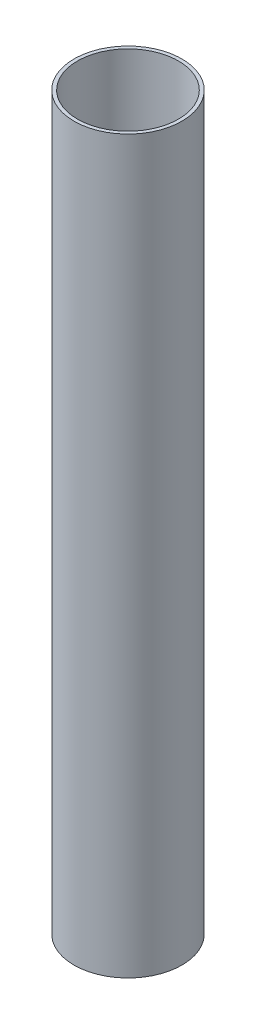
SolidWorks part; units mm, degrees
ref_plane "Front Plane" through (0, 0, 0) normal (0, 0, 1) x (1, 0, 0)
ref_plane "Top Plane" through (0, 0, 0) normal (0, 1, 0) x (1, 0, 0)
ref_plane "Right Plane" through (0, 0, 0) normal (1, 0, 0) x (0, 0, -1)
sketch "Sketch1" plane through (0, 0, 0) normal (0, 1, 0) x (1, 0, 0)
  circle A0 centre (0, 0) radius 14.5
  circle A1 centre (0, 0) radius 15.5
  dimension "D1" = 29
  dimension "D2" = 1
extrude "Boss-Extrude1" add sketch "Sketch1" along normal blind 210
